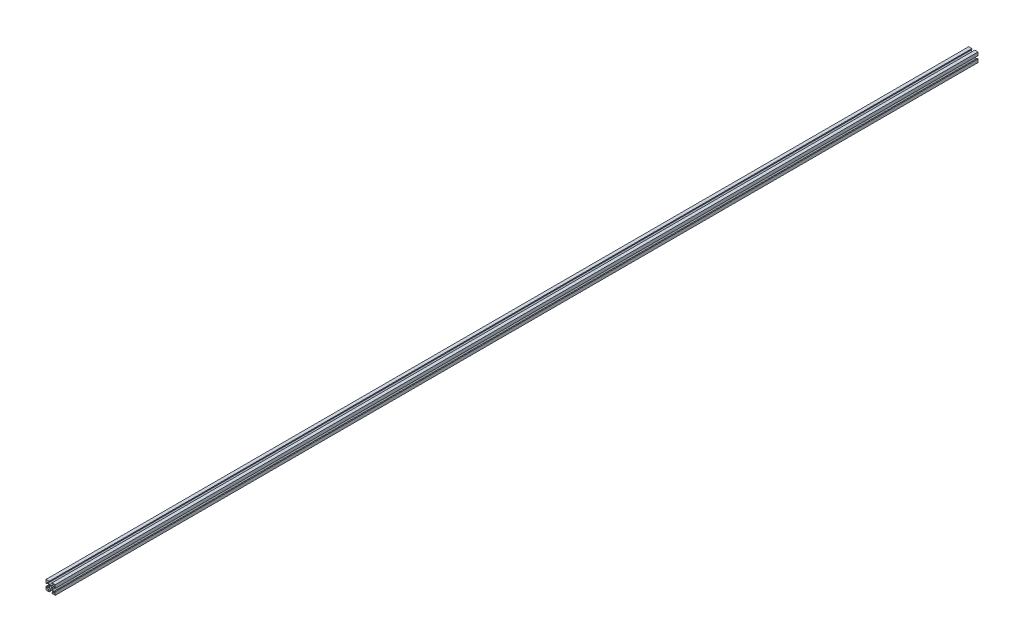
SolidWorks part; units mm, degrees
ref_plane "Front Plane" through (0, 0, 0) normal (0, 0, 1) x (1, 0, 0)
ref_plane "Top Plane" through (0, 0, 0) normal (0, 1, 0) x (1, 0, 0)
ref_plane "Right Plane" through (0, 0, 0) normal (1, 0, 0) x (0, 0, -1)
sketch "Esquisse1" plane through (0, 0, 0) normal (0, 0, 1) x (1, 0, 0)
  line L0 (0, 2) -> (0, 1.25)
  line L1 (-3.0678, 3.7351) -> (-1, 2)
  line L2 (-2.9714, 4) -> (-1.5, 4)
  line L3 (-1.5, 4) -> (-1.5, 5)
  line L4 (-5, 5) -> (-5, 1.5)
  line L5 (-5, 1.5) -> (-4, 1.5)
  line L6 (-4, 1.5) -> (-4, 2.9714)
  line L7 (-5, 5) -> (-1.5, 5)
  line L8 (-3.7351, 3.0678) -> (-2, 1)
  line L9 (-2, 1) -> (-2, 0)
  line L10 (-2, 0) -> (-1.25, 0)
  line L11 (-1, 2) -> (0, 2)
  arc A0 (-2.9714, 4) -> (-3.0678, 3.7351) centre (-2.9714, 3.85) ccw
  arc A1 (-4, 2.9714) -> (-3.7351, 3.0678) centre (-3.85, 2.9714) cw
  arc A2 (0, 1.25) -> (-1.25, 0) centre (0, 0) ccw
  dimension "D7" = 0.15
  dimension "D4" = 1.25
  dimension "D1" = 3.5
  dimension "D2" = 1
  dimension "D3" = 1
  dimension "D5" = 5
  dimension "D6" = 2
  dimension "D8" = 5
  dimension "D9" = 40
ref_axis "Axe1" through (0, -0.1269, 0) along (0, 1, 0)
extrude "Boss.-Extru.1" add sketch "Esquisse1" along normal blind 1000
ref_axis "Axe2" through (0, 0, 105) along (0, 0, -1)
pattern_circular "Répétition circulaire1" count 4 every 90 about axis through (0, 0, 105) along (0, 0, -1) of "Boss.-Extru.1"
